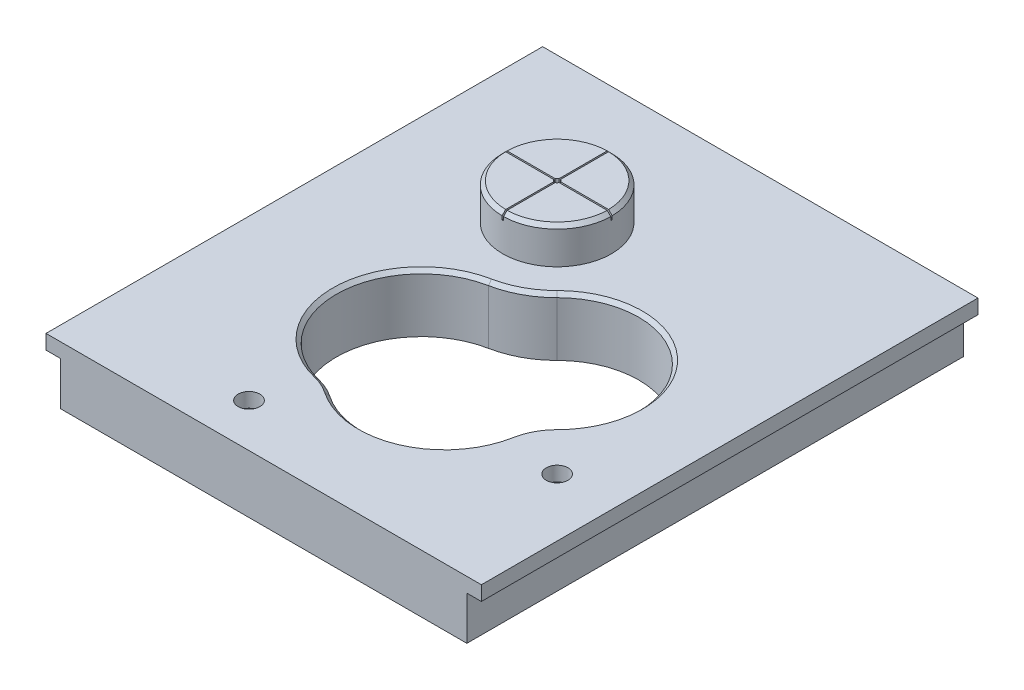
SolidWorks part; units mm, degrees
ref_plane "Front Plane" through (0, 0, 0) normal (0, 0, 1) x (1, 0, 0)
ref_plane "Top Plane" through (0, 0, 0) normal (0, 1, 0) x (1, 0, 0)
ref_plane "Right Plane" through (0, 0, 0) normal (1, 0, 0) x (0, 0, -1)
sketch "Sketch1" plane through (0, 0, 0) normal (0, 1, 0) x (1, 0, 0)
  line L0 (0, 0) -> (30.052, -30.052) construction
  line L1 (0, -42.5) -> (0, 0) construction
  line L3 (-20, 20) -> (36.052, 20)
  line L4 (-20, 20) -> (-20, -48.5)
  line L5 (-20, -48.5) -> (36.052, -48.5)
  line L6 (36.052, 20) -> (36.052, -48.5)
  circle A0 centre (0, 0) radius 7.5
  circle A1 centre (0, -42.5) radius 1.5
  circle A2 centre (30.052, -30.052) radius 1.5
  dimension "D3" = 3
  dimension "D4" = 3
  dimension "D5" = 15
  dimension "D1" = 42.5
  dimension "D2" = 42.5
  dimension "D6" = 45
  dimension "D7" = 6
  dimension "D8" = 6
  dimension "D9" = 20
  dimension "D10" = 20
extrude "Boss-Extrude1" add sketch "Sketch1" against normal blind 8 contours A0 | L6 L3 L4 L5 A2 A1 A0 region at (8.3876, 0, 14.8548) region at (0, 0, 0)
extrude "Boss-Extrude2" add sketch "Sketch1<3>" along normal blind 5 contours A0 region at (0, 0, 0)
sketch "Sketch1<3>" plane through (0, 0, 0) normal (0, 1, 0) x (1, 0, 0) same geometry as "Sketch1"
sketch "Sketch2" plane through (0, -8, 0) normal (0, -1, 0) x (1, 0, 0)
  circle A0 centre (0, 42.5) radius 1.9
  circle A1 centre (30.052, 30.052) radius 1.9
  circle M1 centre (30.052, 30.052) radius 1.5
  circle M2 centre (0, 42.5) radius 1.5
  dimension "D1" = 3.8
extrude "Cut-Extrude1" cut sketch "Sketch2" against normal blind 6 contours A0 M2 | A1 M1 region at (-1.8463, -8, 42.5) region at (28.2058, -8, 30.052)
sketch "Sketch3" plane through (0, 0, 48.5) normal (0, 0, 1) x (1, 0, 0)
  line L1 (-20, 0) -> (-22, 0)
  line L2 (-20, 0) -> (-20, -2)
  line L3 (-20, -2) -> (-22, -2)
  line L4 (-22, 0) -> (-22, -2)
  line L5 (36.052, 0) -> (38.052, 0)
  line L6 (36.052, 0) -> (36.052, -2)
  line L7 (36.052, -2) -> (38.052, -2)
  line L8 (38.052, 0) -> (38.052, -2)
  dimension "D1" = 2
  dimension "D2" = 2
extrude "Boss-Extrude3" add sketch "Sketch3" against normal up to surface (68.5 mm away) up to face at (8.026, -4, -20)
sketch "Sketch4" plane through (0, 0, 0) normal (0, 1, 0) x (1, 0, 0)
  arc A0 (8.4853, -8.4853) -> (2.3202, -11.7736) centre (0, 0) cw
  arc A1 (4.5347, -35.9093) -> (1.8601, -34.7193) centre (0, -42.5) ccw
  arc A2 (2.3202, -11.7736) -> (1.8601, -34.7193) centre (4.591, -23.2966) ccw
  arc A3 (22.1852, -28.5982) -> (24.3952, -24.3952) centre (30.052, -30.052) cw
  arc A4 (8.4853, -8.4853) -> (24.3952, -24.3952) centre (16.4402, -16.4402) cw
  arc A5 (22.1852, -28.5982) -> (4.5347, -35.9093) centre (10.9887, -26.5291) cw
  dimension "D1" = 8
  dimension "D2" = 8
  dimension "D3" = 12
extrude "Cut-Extrude2" cut sketch "Sketch4" against normal blind 10
sketch "Sketch5" plane through (0, 5, 0) normal (0, 1, 0) x (1, 0, 0)
  line L0 (0, 0) -> (0, 7.5) construction
  line L1 (0, 0) -> (-7.5, 0) construction
  line L2 (-7.4993, 0.1) -> (-0.1, 0.1)
  line L3 (-0.1, 0.1) -> (-0.1, 7.4993)
  line L4 (0.1, 0.1) -> (0.1, 7.4993)
  line L5 (7.4993, 0.1) -> (0.1, 0.1)
  line L6 (7.4993, -0.1) -> (0.1, -0.1)
  line L7 (0.1, -0.1) -> (0.1, -7.4993)
  line L8 (-0.1, -0.1) -> (-0.1, -7.4993)
  line L9 (-7.4993, -0.1) -> (-0.1, -0.1)
  circle A0 centre (0, 0) radius 7.5 construction
  circle A1 centre (0, 0) radius 0.375
  arc A2 (7.4993, -0.1) -> (7.4993, 0.1) centre (0, 0) ccw
  arc A3 (-0.1, -7.4993) -> (0.1, -7.4993) centre (0, 0) ccw
  arc A4 (-7.4993, 0.1) -> (-7.4993, -0.1) centre (0, 0) ccw
  arc A5 (0.1, 7.4993) -> (-0.1, 7.4993) centre (0, 0) ccw
  dimension "D3" = 0.75
  dimension "D1" = 0.1
  dimension "D2" = 0.1
  dimension "D4" = 4
extrude "Cut-Extrude3" cut sketch "Sketch5" against normal blind 1 contours L8 L7 L6 A2 L5 L4 L3 L2 L9 | A1 L2 L9 | L3 A1 L2 | L9 A1 L8 | L7 A1 L6 | A1 L8 L7 | A1 L6 A2 L5 | A1 L4 L3 | L5 A1 L4 region at (-3.9351, 5, 0) region at (-0.2022, 5, -0.2022) region at (0, 5, 0) region at (0, 5, -3.9351) region at (-0.2022, 5, 0.2022) region at (0.2022, 5, -0.2022) region at (0, 5, 3.9351) region at (3.9351, 5, 0) region at (0.2022, 5, 0.2022)
chamfer "Chamfer2" distance 0.5 angle 45 4 edges at (5.3033, 5, 5.3033) (5.3033, 5, -5.3033) (-5.3033, 5, -5.3033) (-5.3033, 5, 5.3033)
chamfer "Chamfer3" distance 0.5 angle 45 6 edges at (3.2523, 0, 35.1909) (15.346, 0, 37.0485) (22.9712, 0, 26.329) (24.3952, 0, 8.4853) (5.6474, 0, 10.5881) (-7.1513, 0, 23.0611)
